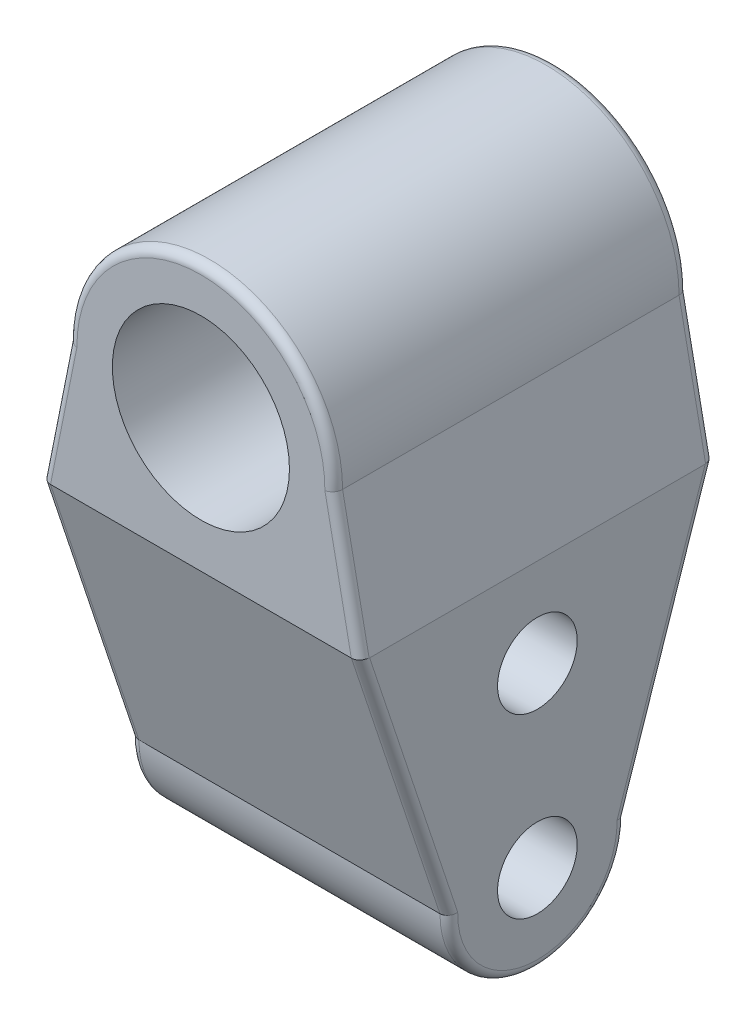
SolidWorks part; units mm, degrees
ref_plane "前视基准面" through (0, 0, 0) normal (0, 0, 1) x (1, 0, 0)
ref_plane "上视基准面" through (0, 0, 0) normal (0, 1, 0) x (1, 0, 0)
ref_plane "右视基准面" through (0, 0, 0) normal (1, 0, 0) x (0, 0, -1)
sketch "草图1" plane through (0, 0, 0) normal (0, 0, 1) x (1, 0, 0)
  line L0 (0, 15) -> (0, -55) construction
  line L1 (0, -55) -> (18, -55)
  line L2 (0, -55) -> (-18, -55)
  line L3 (-18, -55) -> (-18, -15)
  line L4 (-18, -15) -> (-15, 0)
  line L5 (18, -55) -> (18, -15)
  line L6 (18, -15) -> (15, 0)
  arc A0 (15, 0) -> (-15, 0) centre (0, 0) ccw
  circle A1 centre (0, 0) radius 10
extrude "凸台-拉伸1" add sketch "草图1" along normal mid plane 40
sketch "草图2" plane through (0, 0, 0) normal (1, 0, 0) x (0, 0, -1)
  line L0 (0, -55) -> (0, -45) construction
  line L1 (-20, -55) -> (20, -55) construction
  line L2 (0, -45) -> (0, -25) construction
  line L3 (-20, 15) -> (-20, -15) construction
  line L4 (-20, -55) -> (-20, -15) construction
  line L5 (-20, -15) -> (-20, 0) construction
  line L6 (-20, -15) -> (-10, -45)
  line L7 (20, -15) -> (10, -45)
  circle A0 centre (0, -45) radius 4.5
  circle A1 centre (0, -25) radius 4.5
  arc A2 (-10, -45) -> (10, -45) centre (0, -45) ccw
extrude "切除-拉伸1" cut sketch "草图2" against normal mid plane 40 contours A1 | A0
sketch "草图4" plane through (0, 0, 0) normal (1, 0, 0) x (0, 0, -1)
  line L0 (-20, -15) -> (-10, -45)
  line L1 (20, -15) -> (10, -45)
  arc A0 (-10, -45) -> (10, -45) centre (0, -45) ccw
extrude "切除-拉伸6" cut sketch "草图4" against normal through all both and the other way through all
fillet "圆角1" radius 1 12 edges at (-16.5, -7.5, -20) (-18, -30, -15) (-18, -55, 0) (-18, -30, 15) (-16.5, -7.5, 20) (0, 15, 20) (16.5, -7.5, 20) (18, -30, 15) (18, -55, 0) (18, -30, -15) (16.5, -7.5, -20) (0, 15, -20)
sketch "草图5" plane through (0, 0, 0) normal (1, 0, 0) x (0, 0, -1)
  line L0 (0, 0) -> (0, -100)
